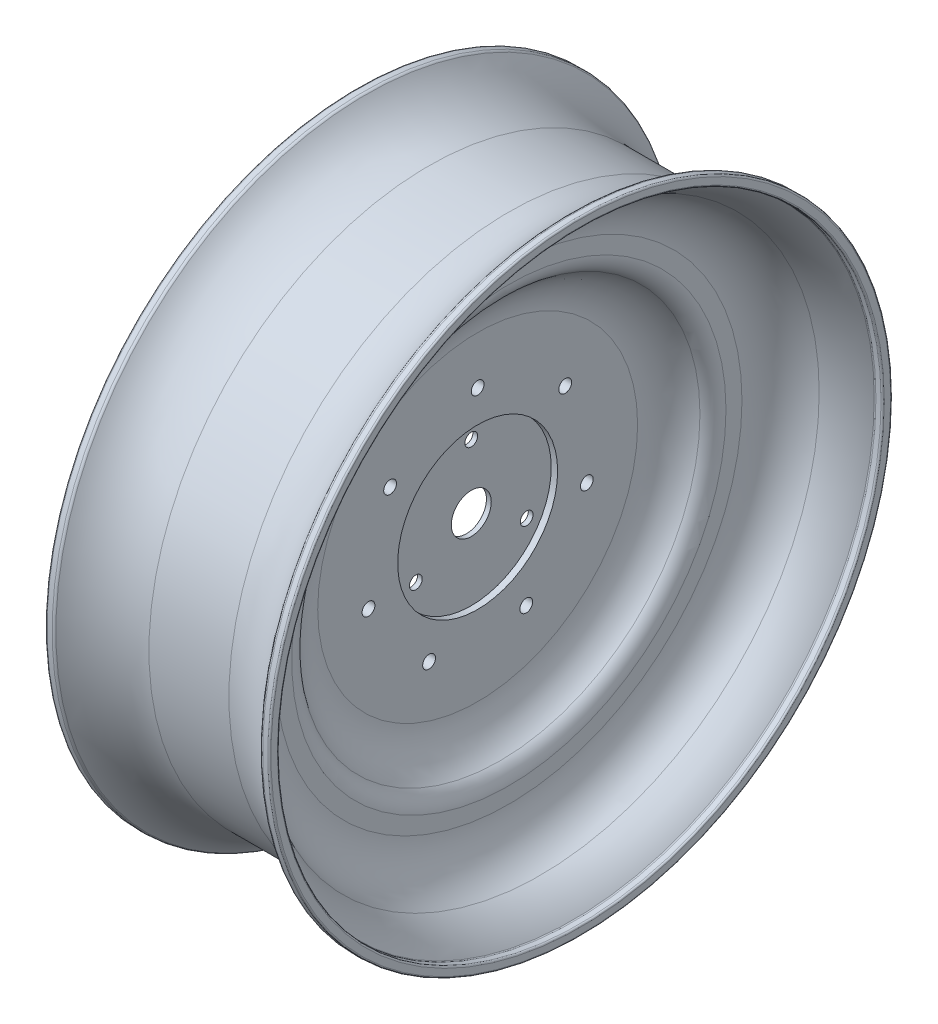
SolidWorks part; units mm, degrees
ref_plane "前视基准面" through (0, 0, 0) normal (0, 0, 1) x (1, 0, 0)
ref_plane "上视基准面" through (0, 0, 0) normal (0, 1, 0) x (1, 0, 0)
ref_plane "右视基准面" through (0, 0, 0) normal (1, 0, 0) x (0, 0, -1)
sketch "草图1" plane through (0, 0, 0) normal (0, 0, 1) x (1, 0, 0)
  line L0 (1.5, 0) -> (-1.5, 0)
  line L1 (-5.5, 50) -> (-5.5, 100)
  line L2 (69, 194.7454) -> (65.7877, 194.7454)
  line L3 (-25, 135.7457) -> (-25, 145.7468)
  line L4 (-65.7877, 188.7013) -> (-69, 188.7013)
  line L5 (-70, 189.7013) -> (-70, 193.7454)
  line L6 (-69, 194.7454) -> (-65.7877, 194.7454)
  line L7 (-25, 175) -> (25, 175)
  line L8 (0, 0) -> (0, 1264.5047) construction
  line L9 (70, 189.7013) -> (70, 193.7454)
  line L10 (65.7877, 188.7013) -> (69, 188.7013)
  line L11 (25, 135.7457) -> (25, 145.7468)
  line L12 (5.5, 50) -> (5.5, 100)
  line L13 (-5.5, 50) -> (-1.5, 50)
  line L14 (-1.5, 50) -> (-1.5, 0)
  line L15 (5.5, 50) -> (1.5, 50)
  line L16 (1.5, 50) -> (1.5, 0)
  arc A0 (-5.5, 100) -> (-19.2605, 125.2246) centre (-35.5, 100) ccw
  arc A1 (-19.2605, 125.2246) -> (-25, 135.7457) centre (-12.487, 135.7457) cw
  arc A2 (-25, 145.7468) -> (-44.6215, 174.4007) centre (-55.733, 145.7468) ccw
  arc A3 (-44.6215, 174.4007) -> (-65.0498, 188.3762) centre (-25, 225) cw
  arc A4 (-65.7877, 194.7454) -> (-64.219, 193.9859) centre (-65.7877, 192.7454) cw
  arc A5 (-64.219, 193.9859) -> (-25, 175) centre (-25, 225) ccw
  arc A6 (-70, 193.7454) -> (-69, 194.7454) centre (-69, 193.7454) cw
  arc A7 (-69, 188.7013) -> (-70, 189.7013) centre (-69, 189.7013) cw
  arc A8 (-65.0498, 188.3762) -> (-65.7877, 188.7013) centre (-65.7877, 187.7013) ccw
  arc A9 (65.0498, 188.3762) -> (65.7877, 188.7013) centre (65.7877, 187.7013) cw
  arc A10 (69, 188.7013) -> (70, 189.7013) centre (69, 189.7013) ccw
  arc A11 (70, 193.7454) -> (69, 194.7454) centre (69, 193.7454) ccw
  arc A12 (64.219, 193.9859) -> (25, 175) centre (25, 225) cw
  arc A13 (65.7877, 194.7454) -> (64.219, 193.9859) centre (65.7877, 192.7454) ccw
  arc A14 (44.6215, 174.4007) -> (65.0498, 188.3762) centre (25, 225) ccw
  arc A15 (25, 145.7468) -> (44.6215, 174.4007) centre (55.733, 145.7468) cw
  arc A16 (19.2605, 125.2246) -> (25, 135.7457) centre (12.487, 135.7457) ccw
  arc A17 (5.5, 100) -> (19.2605, 125.2246) centre (35.5, 100) cw
  point P143 (0, 175)
  dimension "D5" = 4
  dimension "D6" = 25
  dimension "D7" = 1
  dimension "D8" = 2
  dimension "D9" = 50
  dimension "D10" = 4
  dimension "D2" = 30
  dimension "D3" = 50
  dimension "D4" = 175
  dimension "D11" = 70
  dimension "D12" = 100
  dimension "D13" = 3
revolve "旋转1" add sketch "草图1" angle 360 about L0
sketch "草图2" plane through (-1.5, 0, 0) normal (-1, 0, 0) x (0, 0, 1)
  circle A0 centre (0, 0) radius 40 construction
  circle A1 centre (0, 40) radius 4
  dimension "D1" = 80
  dimension "D2" = 8
extrude "切除-拉伸1" cut sketch "草图2" against normal through all both and the other way through all
ref_axis "基准轴1" through (-25, 0, 0) along (1, 0, 0)
pattern_circular "阵列(圆周)1" count 3 over 360 about axis through (-25, 0, 0) along (1, 0, 0) of "切除-拉伸1"
sketch "草图3" plane through (-5.5, 0, 0) normal (-1, 0, 0) x (0, 0, 1)
  circle A0 centre (0, 0) radius 70 construction
  circle A1 centre (0, 70) radius 4
  dimension "D1" = 140
  dimension "D2" = 8
extrude "切除-拉伸2" cut sketch "草图3" against normal through all both and the other way through all
pattern_circular "阵列(圆周)2" count 7 over 360 about axis through (-25, 0, 0) along (1, 0, 0) of "切除-拉伸2"
sketch "草图4" plane through (-1.5, 0, 0) normal (-1, 0, 0) x (0, 0, 1)
  circle A0 centre (0, 0) radius 12.5
  dimension "D1" = 25
extrude "切除-拉伸3" cut sketch "草图4" against normal through all both and the other way through all
